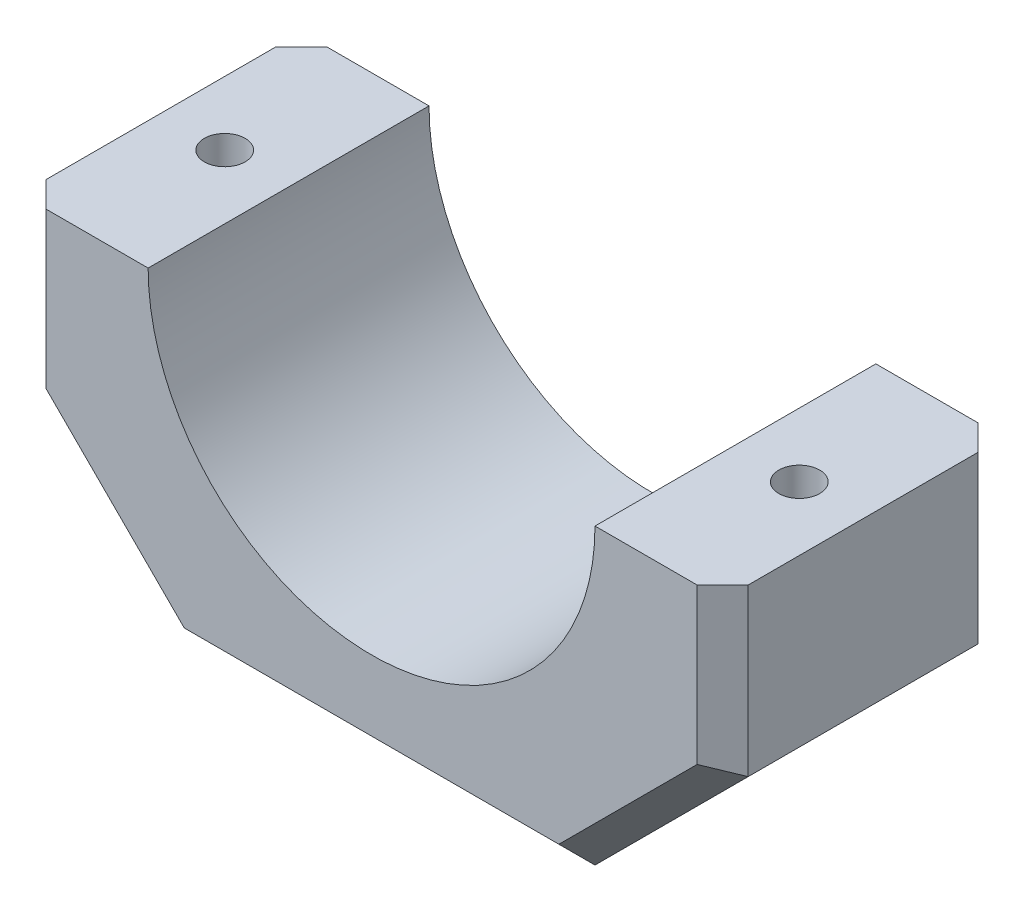
SolidWorks part; units mm, degrees
ref_plane "Front Plane" through (0, 0, 0) normal (0, 0, 1) x (1, 0, 0)
ref_plane "Top Plane" through (0, 0, 0) normal (0, 1, 0) x (1, 0, 0)
ref_plane "Right Plane" through (0, 0, 0) normal (1, 0, 0) x (0, 0, -1)
sketch "Sketch1" plane through (0, 0, 0) normal (0, 0, -1) x (1, 0, 0)
  line L0 (-38.9855, -2.0289) -> (-48.9855, -2.0289)
  line L1 (-48.9855, -2.0289) -> (-48.9855, 22.9711)
  line L2 (-48.9855, 22.9711) -> (6.0145, 22.9711)
  line L3 (6.0145, 22.9711) -> (6.0145, -2.0289)
  line L4 (6.0145, -2.0289) -> (-3.9855, -2.0289)
  arc A0 (-38.9855, -2.0289) -> (-3.9855, -2.0289) centre (-21.4855, -2.0289) cw
  dimension "D1" = 17.5
  dimension "D2" = 10
  dimension "D3" = 25
extrude "Boss-Extrude1" add sketch "Sketch1" along normal blind 22
chamfer "Chamfer1" distance 12 distance2 12 2 edges at (6.0145, -22.9711, -11) (-48.9855, -22.9711, -11)
sketch "Sketch2" plane through (0, -22.9711, 0) normal (0, -1, 0) x (-1, 0, 0)
  line L0 (48.9855, 22) -> (48.9855, 0) construction
  line L1 (-6.0145, 22) -> (-6.0145, 0) construction
  line L2 (5.9855, 0) -> (36.9855, 0) construction
  circle A0 centre (-1.0145, 11) radius 1.6
  circle A1 centre (43.9855, 11) radius 1.6
  circle A2 centre (43.9855, 11) radius 3
  circle A3 centre (-1.0145, 11) radius 3
  point P8 (-6.0145, 11)
  dimension "D4" = 3.2
  dimension "D5" = 6
  dimension "D1" = 5
  dimension "D2" = 5
  dimension "D3" = 11
extrude "Cut-Extrude1" cut sketch "Sketch2" against normal up to surface (25 mm away) contours A1 | A0 region at (1.0145, -22.9711, -11) region at (-43.9855, -22.9711, -11) up to face at (-43.9855, 2.0289, -11)
extrude "Cut-Extrude2" cut sketch "Sketch2<4>" against normal offset from surface (21 mm away) 4 up to face at (-42.3855, 2.0289, -11)
sketch "Sketch2<4>" plane through (0, -22.9711, 0) normal (0, -1, 0) x (-1, 0, 0) same geometry as "Sketch2"
chamfer "Chamfer2" distance 2 angle 45 10 edges at (-48.9855, -4.4711, 0) (-42.9855, -16.9711, 0) (6.0145, -4.4711, 0) (-21.4855, -22.9711, 0) (0.0145, -16.9711, 0) (6.0145, -4.4711, -22) (-48.9855, -4.4711, -22) (-42.9855, -16.9711, -22) (-21.4855, -22.9711, -22) (0.0145, -16.9711, -22)
